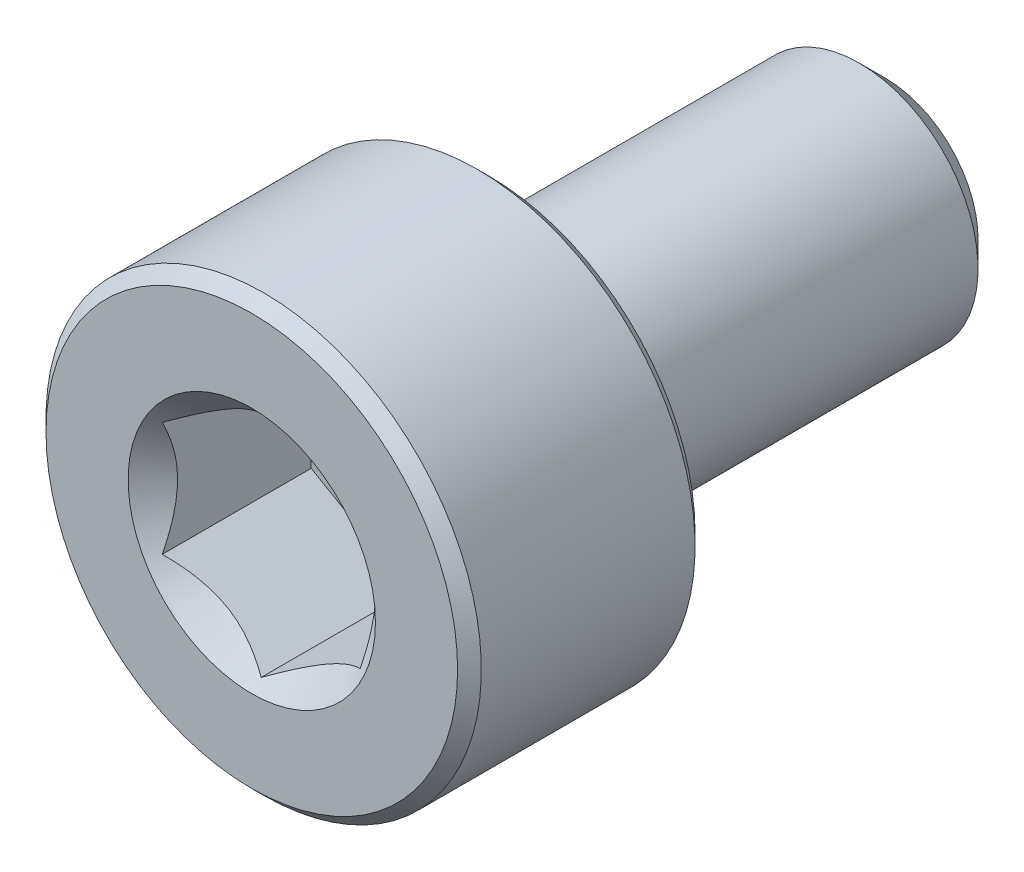
SolidWorks part; units mm, degrees
ref_plane "Front Plane" through (0, 0, 0) normal (0, 0, 1) x (1, 0, 0)
ref_plane "Top Plane" through (0, 0, 0) normal (0, 1, 0) x (1, 0, 0)
ref_plane "Right Plane" through (0, 0, 0) normal (1, 0, 0) x (0, 0, -1)
sketch "Sketch1" plane through (0, 0, 0) normal (1, 0, 0) x (0, 0, -1)
  line L0 (-4, 0) -> (4, 0) construction
  line L1 (4, 0) -> (4, 1.1752) construction
  line L2 (4, 1.1752) -> (3.6752, 1.5) construction
  line L3 (3.6752, 1.5) -> (3.625, 1.5) construction
  line L4 (3.625, 1.5) -> (-1, 1.5) construction
  line L5 (-1, 1.5) -> (-1, 2.75) construction
  line L6 (-1, 2.75) -> (-4, 2.75) construction
  line L7 (-4, 2.75) -> (-4, 0) construction
  line L8 (4, 1.1752) -> (4, 1.5) construction
  line L9 (3.9688, 1.5541) -> (4.2188, 1.1211) construction
  line L10 (4.2188, 1.1211) -> (4.4688, 1.5541) construction
  line L11 (4.4688, 1.5541) -> (3.9688, 1.5541) construction
  line L12 (4.2188, 1.5541) -> (4.2188, 1.5) construction
  line L13 (4.2188, 1.1211) -> (4.2188, 1.1752) construction
  line L14 (4.1875, 1.1752) -> (4.25, 1.1752) construction
  line L15 (4, 1.5) -> (4.4375, 1.5) construction
  line L16 (3.9844, 1.5271) -> (4.4531, 1.5271) construction
  line L17 (4, 0) -> (4, -1.5) construction
  line L18 (-1.15, 2.75) -> (-1, 2.6) construction
  line L19 (-3.85, 2.75) -> (-4, 2.6) construction
  line L20 (-1, 1.5) -> (-1, 0) construction
  line L21 (-1, 0.75) -> (0.6667, 0.75) construction
  line L22 (0.6667, 0.75) -> (2.3333, 0.75) construction
  line L23 (2.3333, 0.75) -> (4, 0.75) construction
  line L24 (0.6667, 0.75) -> (0.6667, 1.5) construction
  line L25 (0.6667, 1.5) -> (0.6667, 2.75) construction
  line L26 (2.3333, 0.75) -> (2.3333, 2.75) construction
  point P0 (-4, 1.25)
  point P3 (2.75, 1.5)
  point P4 (0, 0)
  point P18 (2.3333, 1.5)
  point P22 (4.2188, 1.1752)
  point P24 (3.625, 1.5)
  point P25 (4.2188, 1.5)
  point P28 (4.2188, 1.5271)
  point P29 (2.75, -1.5)
  point P30 (0.6667, 1.5)
  point P31 (-2.5, 2.75)
  point P37 (-1.525, 2.75)
  point P38 (-3.775, 2.75)
  point P45 (0.6667, 0.75)
  point P46 (2.3333, 0.75)
  dimension "D2" = 0.0625
  dimension "D7" = 0.15
  dimension "D8" = 0.15
  dimension "D9" = 0.15
  dimension "D10" = 0.075
  dimension "D11" = 0.375
  dimension "Drive Size" = 2.5
  dimension "Head Diameter" = 5.5
  dimension "Head Height" = 3
  dimension "Thread Pitch" = 0.5
  dimension "Thread Size" = 3
  dimension "Length" = 5
  dimension "D12" = 0.375
  dimension "D4" = 1.25
  dimension "D3" = 45
sketch "Sketch2" plane through (0, 0, 0) normal (1, 0, 0) x (0, 0, -1)
  line L0 (-4, 0) -> (-4, 2.6)
  line L1 (-3.85, 2.75) -> (-1.15, 2.75)
  line L2 (-1, 2.6) -> (-1, 1.65)
  line L4 (3.6752, 1.5) -> (4, 1.1752)
  line L5 (4, 1.1752) -> (4, 0)
  line L6 (-1, 2.75) -> (-4, 2.75) construction
  line L7 (4, 0) -> (-4, 0)
  line L8 (-3.85, 2.75) -> (-4, 2.6) construction
  line L10 (-3.85, 2.75) -> (-4, 2.6)
  line L14 (-1.15, 2.75) -> (-1, 2.6) construction
  line L16 (-1.15, 2.75) -> (-1, 2.6)
  line L17 (-1, 1.5) -> (-1, 2.75) construction
  line L19 (-0.85, 1.5) -> (3.6752, 1.5)
  line L20 (3.625, 1.5) -> (-1, 1.5) construction
  arc A1 (-1, 1.65) -> (-0.85, 1.5) centre (-0.85, 1.65) ccw
  dimension "D3" = 0.15
revolve "Revolve1" add sketch "Sketch2" angle 360 about L7
sketch "Sketch3" plane through (0, 0, 4) normal (0, 0, 1) x (1, 0, 0)
  line L1 (1.25, -0.7217) -> (1.25, 0.7217)
  line L2 (1.25, 0.7217) -> (0, 1.4434)
  line L3 (0, 1.4434) -> (-1.25, 0.7217)
  line L4 (-1.25, 0.7217) -> (-1.25, -0.7217)
  line L5 (-1.25, -0.7217) -> (0, -1.4434)
  line L6 (0, -1.4434) -> (1.25, -0.7217)
  circle A0 centre (0, 0) radius 1.25 construction
  circle A1 centre (0, 0) radius 2.75 construction
  circle A2 centre (0, 0) radius 2.75 construction
  circle A3 centre (0, 0) radius 1.4434 construction
  point P13 (0, 0)
extrude "Cut-Extrude1" cut sketch "Sketch3" against normal offset from surface (2 mm away) 1 up to face at (0, 2.6, 1)
sketch "Sketch4" plane through (0, 0, 4) normal (0, 0, 1) x (1, 0, 0)
  circle A0 centre (0, 0) radius 1.5625
  dimension "D1" = 3.125
extrude "Cut-Extrude2" cut sketch "Sketch4" against normal up to vertex (1.5 mm away) draft 45 up to point (0, 2.75, 2.5)
sketch "Sketch11" plane through (0, 0, 0) normal (1, 0, 0) x (0, 0, -1)
  line L0 (-4, 0) -> (4, 0) construction
  line L1 (-4, 0) -> (4, 0) construction
  line L2 (-0.0625, 0) -> (-0.0625, 1.5) construction
  line L3 (3.625, 1.5) -> (-1, 1.5) construction
  line L4 (3.0625, 0) -> (3.0625, 1.5) construction
  line L6 (4, 1.1752) -> (4, 1.5) construction
  point P2 (-0.0625, 0)
  point P3 (3.0625, 0)
  dimension "D1" = 0.9375
  dimension "D2" = 0.9375
sketch "Sketch6" [suppressed] plane through (0, 0, -4) normal (0, 0, -1) x (-1, 0, 0)
  circle A0 centre (0, 0) radius 1.5
curve "Helix/Spiral1" [suppressed] pitch 0.5 height 5.5 turns 11
sketch "Sketch10" [suppressed] plane through (0, 0, 0) normal (1, 0, 0) x (0, 0, -1)
  line L0 (-0.85, -2.75) -> (-0.85, 2.75)
  line L5 (-4, 0) -> (4, 0) construction
  line L6 (-0.85, 1.5) -> (-0.85, -1.5) construction
  point P3 (-0.85, 0)
split "Split1" [suppressed] bodies to split 106
sketch "Sketch7" [suppressed] plane through (0, 0, 0) normal (1, 0, 0) x (0, 0, -1)
  line L0 (3.9844, 1.5271) -> (4.4531, 1.5271)
  line L1 (4.4531, 1.5271) -> (4.25, 1.1752)
  line L2 (4.25, 1.1752) -> (4.1875, 1.1752)
  line L3 (4.1875, 1.1752) -> (3.9844, 1.5271)
sweep "Cut-Sweep1" [suppressed] cut profiles "Sketch7" path "Helix/Spiral1"
sketch "Sketch8" [suppressed] plane through (0, 0, 0) normal (1, 0, 0) x (0, 0, -1)
  line L0 (-1, 0) -> (-1, 1.5)
  line L1 (-0.85, -1.5) -> (-0.85, 1.5) construction
  line L2 (-1, 1.5) -> (-0.85, 1.5)
  line L4 (-0.85, 1.5) -> (0.016, 0)
  line L5 (0.016, 0) -> (-1, 0)
  line L6 (3.625, 1.5) -> (-1, 1.5) construction
  line L7 (-4, 0) -> (4, 0) construction
  dimension "D1" = 60
revolve "Revolve2" [suppressed] add sketch "Sketch8" angle 360 about L5
ref_plane "Plane1" [suppressed] through (0, 0, 4) normal (0, 0, 1) x (1, 0, 0)
sketch "Sketch12" [suppressed] plane through (0, 0, 4) normal (0, 0, 1) x (1, 0, 0)
  line L0 (0, 0) -> (0.096, 2.7483) construction
  line L1 (0, 0) -> (-0.096, 2.7483) construction
  line L2 (0, 2.6812) -> (0, 2.8187) construction
  line L3 (-0.1664, 2.8187) -> (0.1664, 2.8187)
  line L4 (-0.1664, 2.8187) -> (-0.0493, 2.7017)
  line L5 (0.0493, 2.7017) -> (0.1664, 2.8187)
  circle A0 centre (0, 0) radius 2.75 construction
  arc A1 (-0.0493, 2.7017) -> (0.0493, 2.7017) centre (0, 2.751) ccw
  point P9 (0, 2.8187)
  point P13 (0, 2.75)
  dimension "D1" = 4
  dimension "D2" = 0.0688
extrude "Cut-Extrude3" [suppressed] cut sketch "Sketch12" against normal blind 2.4
pattern_circular "CirPattern1" [suppressed] count 72 over 360 about axis through (0, 0, 4) along (0, 0, -1) of bodies 118
equation "\"D2@Sketch1\" = \"Thread Pitch@Sketch1\" / 8"
equation "\"D4@Helix/Spiral1\" = \"Thread Pitch@Sketch1\""
equation "\"D7@Sketch1\" = \"Head Height@Sketch1\" * .05"
equation "\"D8@Sketch1\"=\"D7@Sketch1\""
equation "\"D9@Sketch1\"=\"D7@Sketch1\""
equation "\"D10@Sketch1\"=\"D7@Sketch1\"/2"
equation "\"D11@Sketch1\"=\"D10@Sketch1\"*5"
equation "\"D4@Sketch1\"=\"Thread Pitch@Sketch1\"*2.5"
equation "\"D12@Sketch1\"=\"Thread Pitch@Sketch1\"*.75"
equation "\"D3@Helix/Spiral1\"=\"Length@Sketch1\"+\"Thread Pitch@Sketch1\""
equation "\"D3@Sketch2\" = \"Thread Size@Sketch1\" * 0.05"
equation "\"D1@Sketch11\"=\"Length@Sketch1\"*0.1875"
equation "\"D2@Sketch11\"=\"D1@Sketch11\""
equation "\"D2@Sketch12\"=\"Head Diameter@Sketch1\"*.0125"
equation "\"D1@Cut-Extrude3\"=\"Head Height@Sketch1\"*.8"
equation "\"D1@CirPattern1\"=\"D3@CirPattern1\"/(1.25*\"D1@Sketch12\")"
equation "\"D1@Sketch4\"=\"Drive Size@Sketch1\"*1.25"
